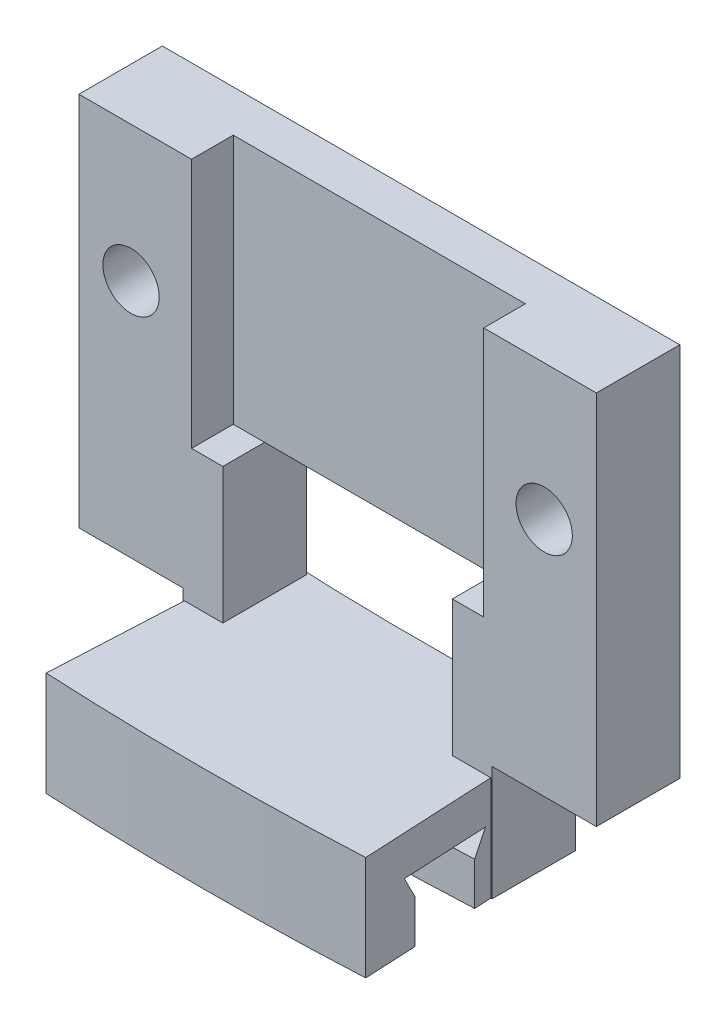
SolidWorks part; units mm, degrees
ref_plane "Front Plane" through (0, 0, 0) normal (0, 0, 1) x (1, 0, 0)
ref_plane "Top Plane" through (0, 0, 0) normal (0, 1, 0) x (1, 0, 0)
ref_plane "Right Plane" through (0, 0, 0) normal (1, 0, 0) x (0, 0, -1)
ref_axis "Axis2" through (0, 11, 0) along (0, -1, 0)
ref_plane "Plane2" through (0, 0, 145.5) normal (0, 0, 1) x (1, 0, 0)
sketch "Sketch7" plane through (0, 0, 145.5) normal (0, 0, 1) x (1, 0, 0)
  line L0 (-12.4, 0) -> (-5.5, 0)
  line L1 (-12.4, 23.5) -> (12.4, 23.5)
  line L2 (-12.4, 23.5) -> (-12.4, 0)
  line L3 (-5.5, 0) -> (-5.5, 11.5)
  line L4 (12.4, 23.5) -> (12.4, 0)
  line L5 (-5.5, 11.5) -> (5.5, 11.5)
  line L6 (5.5, 11.5) -> (5.5, 0)
  line L7 (5.5, 0) -> (12.4, 0)
  point P4 (0, -5)
  point P5 (14.3512, -0.3409)
  point P6 (12.4, 0)
  point P11 (0, 23.5)
  dimension "D1" = 24.8
  dimension "D3" = 11
  dimension "D4" = 11.5
  dimension "D5" = 12
extrude "Main" add sketch "Sketch7" along normal mid plane 4
sketch "Sketch8" plane through (0, 0, 147.5) normal (0, 0, 1) x (1, 0, 0)
  line L0 (12.4, 23.5) -> (-12.4, 23.5) construction
  line L1 (-12.4, 23.5) -> (-12.4, 0) construction
  circle A0 centre (-9.9, 17) radius 1.35
  circle A1 centre (9.9, 17) radius 1.35
  dimension "D1" = 2.7
  dimension "D2" = 19.8
  dimension "D3" = 6.5
  dimension "D4" = 2.5
extrude "Holes" cut sketch "Sketch8" against normal through all
sketch "Sketch9" plane through (0, 0, 147.5) normal (0, 0, 1) x (1, 0, 0)
  line L1 (7, 23.5) -> (-7, 23.5)
  line L2 (7, 23.5) -> (7, 11.5)
  line L3 (7, 11.5) -> (-7, 11.5)
  line L4 (-7, 23.5) -> (-7, 11.5)
  line L5 (-12.4, 23.5) -> (-12.4, 0) construction
  line L6 (12.4, 23.5) -> (-12.4, 23.5) construction
  dimension "D1" = 5.4
  dimension "D2" = 14
  dimension "D3" = 12
extrude "ComponentHoles" cut sketch "Sketch9" against normal blind 2
sketch "Sketch10" plane through (0, 0, 0) normal (1, 0, 0) x (0, 0, -1)
  line L0 (-147.95, 3.1) -> (-152.05, 3.1)
  line L1 (-147.95, 3.1) -> (-148.5, 2.05)
  line L2 (-148.5, 2.05) -> (-148.5, 0)
  line L3 (-148.5, 0) -> (-143.5, 0)
  line L4 (-143.5, 0) -> (-143.5, 5)
  line L5 (-143.5, 5) -> (-154, 5)
  line L6 (-154, 5) -> (-154, 0)
  line L7 (-152.05, 3.1) -> (-151.5, 2.05)
  line L8 (-151.5, 2.05) -> (-151.5, 0)
  line L9 (-151.5, 0) -> (-154, 0)
  point P9 (-150, 3.1)
  dimension "D1" = 3
  dimension "D2" = 5
  dimension "D3" = 4.1
  dimension "D4" = 2.05
  dimension "D5" = 3.1
  dimension "D6" = 5
  dimension "D7" = 150
  dimension "D8" = 5
  dimension "D9" = 2.5
revolve "Support" add sketch "Sketch10" angle 5.7 mid plane about axis through (0, 11, 0) along (0, -1, 0)
sketch "Sketch11" plane through (0, 0, 147.5) normal (0, 0, 1) x (1, 0, 0)
  line L0 (-12.4, 23.5) -> (-12.4, 0) construction
  line L1 (-12.4, 5.5) -> (-7.4, 5.5)
  line L2 (-12.4, 5.5) -> (-12.4, 0)
  line L3 (-12.4, 0) -> (-7.4, 0)
  line L4 (-7.4, 5.5) -> (-7.4, 0)
  line L5 (-12.4, 0) -> (-5.5, 0) construction
  line L6 (12.4, 0) -> (12.4, 23.5) construction
  line L7 (12.4, 5.5) -> (7.4, 5.5)
  line L8 (12.4, 5.5) -> (12.4, 0)
  line L9 (12.4, 0) -> (7.4, 0)
  line L10 (7.4, 5.5) -> (7.4, 0)
  line L11 (5.5, 0) -> (12.4, 0) construction
  dimension "D1" = 5
  dimension "D2" = 5.5
extrude "Support-Cut" cut sketch "Sketch11" against normal through all
